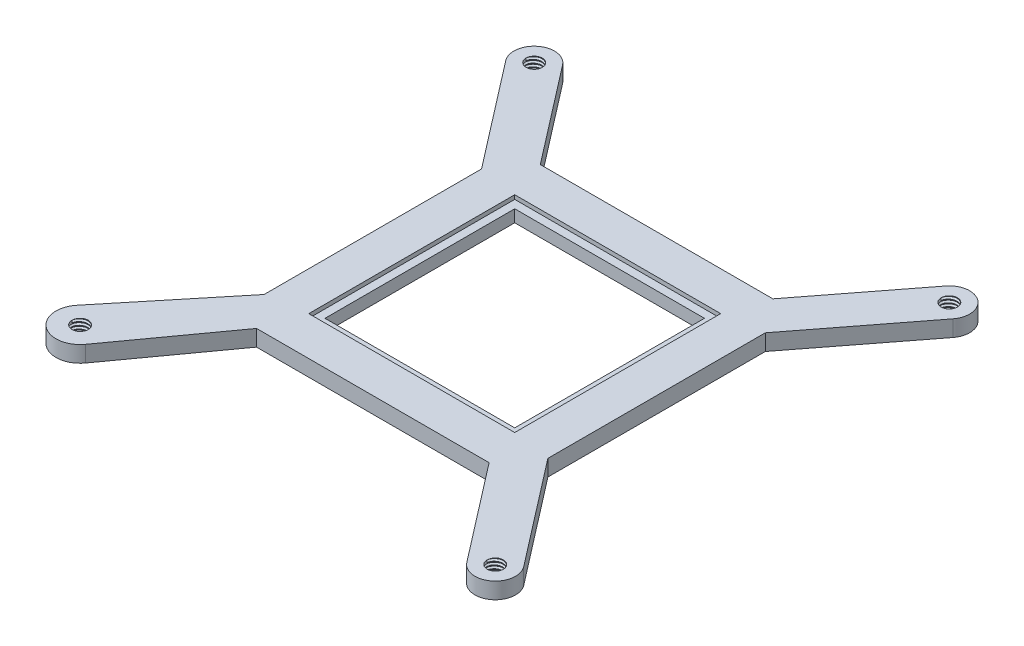
SolidWorks part; units mm, degrees
ref_plane "Front Plane" through (0, 0, 0) normal (0, 0, 1) x (1, 0, 0)
ref_plane "Top Plane" through (0, 0, 0) normal (0, 1, 0) x (1, 0, 0)
ref_plane "Right Plane" through (0, 0, 0) normal (1, 0, 0) x (0, 0, -1)
sketch "Sketch1" plane through (0, 0, 0) normal (0, 1, 0) x (1, 0, 0)
  line L0 (-24.7962, 29.7084) -> (-16.6962, 19.2084) construction
  line L1 (-10.8962, 13.4084) -> (12.5038, 13.4084)
  line L2 (-10.8962, 13.4084) -> (-10.8962, -9.9916)
  line L3 (-10.8962, -9.9916) -> (12.5038, -9.9916)
  line L4 (12.5038, 13.4084) -> (12.5038, -9.9916)
  line L5 (-13.5388, 19.2084) -> (15.1438, 19.2084)
  line L6 (-16.6962, 15.1154) -> (-16.6962, -11.7016)
  line L7 (-13.5388, -15.7916) -> (15.1438, -15.7916)
  line L8 (18.3038, 15.1154) -> (18.3038, -11.7016)
  line L9 (-24.7962, 29.7084) -> (-22.8167, 31.2354) construction
  line L10 (-22.8167, 31.2354) -> (-26.7757, 28.1813) construction
  line L11 (-22.8167, 31.2354) -> (-13.5388, 19.2084)
  line L12 (-26.7757, 28.1813) -> (-16.6962, 15.1154)
  line L13 (-24.7962, -26.2916) -> (-16.6962, -15.7916) construction
  line L14 (-13.5388, -15.7916) -> (-22.3846, -28.0342)
  line L15 (-16.6962, -11.7016) -> (-27.0983, -24.4068)
  line L16 (-13.5388, 19.2084) -> (-13.5388, -15.7916) construction
  line L17 (18.3038, -11.7016) -> (28.3847, -24.7628)
  line L18 (-16.6962, 15.1154) -> (18.3038, 15.1154) construction
  line L19 (15.1438, 19.2084) -> (15.1438, -15.7916) construction
  line L20 (-16.6962, -11.7016) -> (18.3038, -11.7016) construction
  line L21 (15.1438, -15.7916) -> (24.4225, -27.82)
  line L22 (15.1438, 19.2084) -> (24.4244, 31.2357)
  line L23 (18.3038, 15.1154) -> (28.3833, 28.1813)
  circle A0 centre (-24.7962, 29.7084) radius 1
  circle A1 centre (26.4038, 29.7084) radius 1
  circle A2 centre (26.4038, -26.2916) radius 1
  circle A3 centre (-24.7962, -26.2916) radius 1
  arc A4 (-22.8167, 31.2354) -> (-26.7757, 28.1813) centre (-24.7962, 29.7084) ccw
  arc A5 (-27.0983, -24.4068) -> (-22.3846, -28.0342) centre (-24.7962, -26.2916) ccw
  arc A6 (24.4225, -27.82) -> (28.3847, -24.7628) centre (26.4038, -26.2916) ccw
  arc A7 (28.3833, 28.1813) -> (24.4244, 31.2357) centre (26.4038, 29.7084) ccw
  dimension "D7" = 8.1
  dimension "D11" = 3.1574
  dimension "D12" = 4.093
  dimension "D14" = 3.16
  dimension "D1" = 23.4
  dimension "D2" = 23.4
  dimension "D3" = 35
  dimension "D4" = 35
  dimension "D5" = 5.8
  dimension "D6" = 5.8
  dimension "D8" = 10.5
  dimension "D13" = 4.09
  dimension "D15" = 5.8
  dimension "D9" = 2
  dimension "D10" = 2
extrude "Boss-Extrude2" add sketch "Sketch1" along normal blind 2
sketch "Sketch13" plane through (0, 2, 0) normal (0, 1, 0) x (1, 0, 0)
  line L0 (12.5038, 13.4084) -> (-10.8962, 13.4084) construction
  line L1 (-11.8962, 14.4084) -> (13.5038, 14.4084)
  line L2 (-11.8962, 14.4084) -> (-11.8962, -10.9916)
  line L3 (-11.8962, -10.9916) -> (13.5038, -10.9916)
  line L4 (13.5038, 14.4084) -> (13.5038, -10.9916)
  line L5 (12.5038, -9.9916) -> (12.5038, 13.4084) construction
  dimension "D1" = 1
  dimension "D2" = 1
  dimension "D3" = 25.4
  dimension "D4" = 25.4
extrude "Cut-Extrude1" cut sketch "Sketch13" against normal blind 0.5
thread "Thread5" pitch 0.4 method cut profile "Thread Profile5" start angle 0, offset 0, length 2, pitch 0.4, diameter 2
ref_plane "Plane5" through (-25.7962, 2, -29.7084) normal (0, 0, 1) x (-1, 0, 0)
sketch "Thread Profile5" plane through (-25.7962, 2, -29.7084) normal (0, 0, 1) x (-1, 0, 0)
  line L0 (0, 0) -> (0, 0.4) construction
  line L1 (0, 0) -> (0.2165, 0.125)
  line L2 (0.2165, 0.125) -> (0.2165, 0.175)
  line L3 (0.2165, 0.175) -> (0, 0.3)
  line L4 (0.2165, 0.15) -> (0, 0.15) construction
  line L11 (0, 0) -> (0, 0.3)
  point P2 (0, 0)
  dimension "Pitch" = 0.4
  dimension "Profile_Angle" = 60
  dimension "Profile_Land" = 0.05
  dimension "Profile_Height" = 0.2165
thread "Thread6" pitch 0.4 method cut profile "Thread Profile6" start angle 0, offset 0, length 2, pitch 0.4, diameter 2
ref_plane "Plane6" through (25.4038, 2, -29.7084) normal (0, 0, 1) x (-1, 0, 0)
sketch "Thread Profile6" plane through (25.4038, 2, -29.7084) normal (0, 0, 1) x (-1, 0, 0)
  line L0 (0, 0) -> (0, 0.4) construction
  line L1 (0, 0) -> (0.2165, 0.125)
  line L2 (0.2165, 0.125) -> (0.2165, 0.175)
  line L3 (0.2165, 0.175) -> (0, 0.3)
  line L4 (0.2165, 0.15) -> (0, 0.15) construction
  line L11 (0, 0) -> (0, 0.3)
  point P2 (0, 0)
  dimension "Pitch" = 0.4
  dimension "Profile_Angle" = 60
  dimension "Profile_Land" = 0.05
  dimension "Profile_Height" = 0.2165
thread "Thread7" pitch 0.4 method cut profile "Thread Profile7" start angle 0, offset 0, length 2, pitch 0.4, diameter 2
ref_plane "Plane7" through (-25.7962, 2, 26.2916) normal (0, 0, 1) x (-1, 0, 0)
sketch "Thread Profile7" plane through (-25.7962, 2, 26.2916) normal (0, 0, 1) x (-1, 0, 0)
  line L0 (0, 0) -> (0, 0.4) construction
  line L1 (0, 0) -> (0.2165, 0.125)
  line L2 (0.2165, 0.125) -> (0.2165, 0.175)
  line L3 (0.2165, 0.175) -> (0, 0.3)
  line L4 (0.2165, 0.15) -> (0, 0.15) construction
  line L11 (0, 0) -> (0, 0.3)
  point P2 (0, 0)
  dimension "Pitch" = 0.4
  dimension "Profile_Angle" = 60
  dimension "Profile_Land" = 0.05
  dimension "Profile_Height" = 0.2165
thread "Thread8" pitch 0.4 method cut profile "Thread Profile8" start angle 0, offset 0, length 2, pitch 0.4, diameter 2
ref_plane "Plane8" through (25.4038, 2, 26.2916) normal (0, 0, 1) x (-1, 0, 0)
sketch "Thread Profile8" plane through (25.4038, 2, 26.2916) normal (0, 0, 1) x (-1, 0, 0)
  line L0 (0, 0) -> (0, 0.4) construction
  line L1 (0, 0) -> (0.2165, 0.125)
  line L2 (0.2165, 0.125) -> (0.2165, 0.175)
  line L3 (0.2165, 0.175) -> (0, 0.3)
  line L4 (0.2165, 0.15) -> (0, 0.15) construction
  line L11 (0, 0) -> (0, 0.3)
  point P2 (0, 0)
  dimension "Pitch" = 0.4
  dimension "Profile_Angle" = 60
  dimension "Profile_Land" = 0.05
  dimension "Profile_Height" = 0.2165
